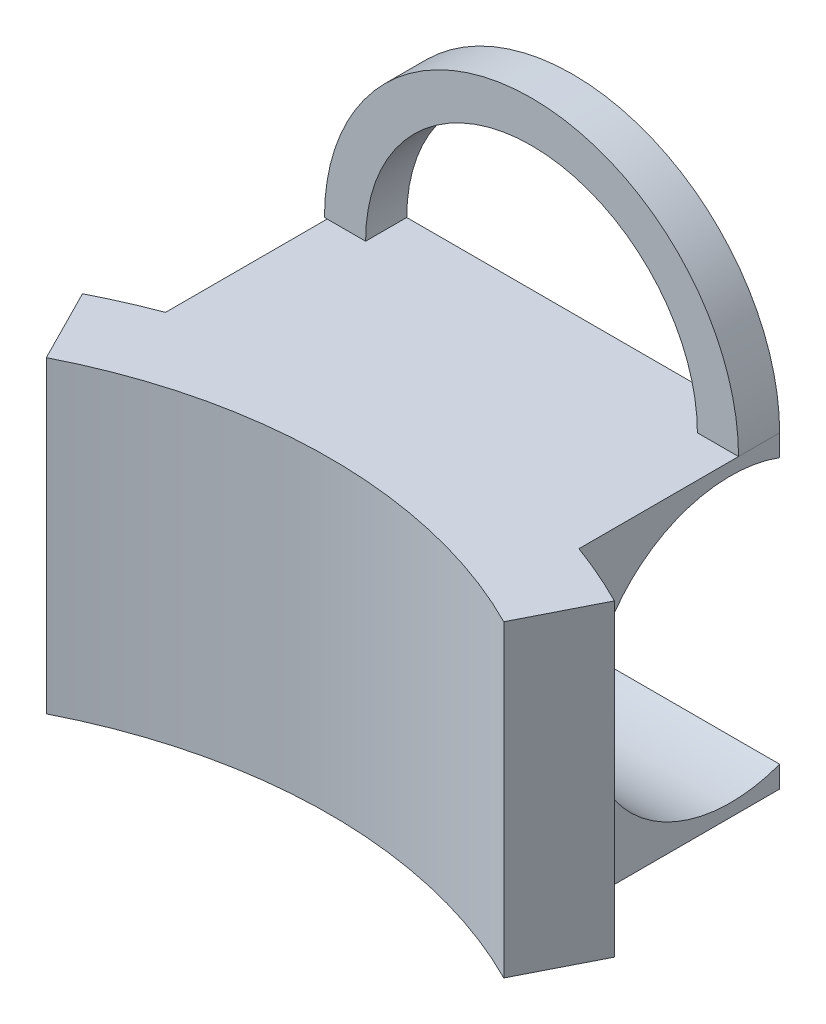
SolidWorks part; units mm, degrees
material "PVC 0.007 Plasticized"
ref_plane "Front Plane" through (0, 0, 0) normal (0, 0, 1) x (1, 0, 0)
ref_plane "Top Plane" through (0, 0, 0) normal (0, 1, 0) x (1, 0, 0)
ref_plane "Right Plane" through (0, 0, 0) normal (1, 0, 0) x (0, 0, -1)
ref_axis "X-Axis" through (-88.99, 0, 0) along (1, 0, 0)
ref_axis "Y-Axis" through (0, 55, 0) along (0, -1, 0)
ref_axis "Z-Axis" through (0, 0, 55) along (0, 0, -1)
sketch "Sketch2" plane through (0, 0, 0) normal (0, 1, 0) x (1, 0, 0)
  line L1 (-6.35, 0) -> (6.35, 0)
  line L2 (-6.35, 0) -> (-6.35, -6.35)
  line L3 (-6.35, -6.35) -> (6.35, -6.35)
  line L4 (6.35, 0) -> (6.35, -6.35)
  point P4 (0, -6.35)
  dimension "D1" = 6.35
  dimension "D2" = 12.7
extrude "Boss-Extrude1" add sketch "Sketch2" against normal blind 9.525
sketch "Sketch3" plane through (0, 0, 0) normal (0, 1, 0) x (1, 0, 0)
  arc A0 (-7.5546, -8.1773) -> (7.7179, -8.1773) centre (0.0817, -23.2191) cw
extrude "Extrude-Thin1" add sketch "Sketch3" against normal blind 9.525 thin thin type mid plane wall 2.54
sketch "Sketch4" plane through (0, 0, 0) normal (1, 0, 0) x (0, 0, -1)
  line L0 (0, -9.525) -> (0, 0) construction
  circle A0 centre (-1.517, -4.7625) radius 4.37
  point P4 (0, -4.7625)
extrude "Cut-Extrude1" cut sketch "Sketch4" against normal through all both and the other way through all contours A0
sketch "Sketch6" plane through (0, 0, 0) normal (0, 0, 1) x (1, 0, 0)
  line L0 (7.143, 0) -> (-6.9797, 0) construction
  arc A0 (-6.4331, 0) -> (6.35, 0) centre (-0.0415, 0) cw
extrude "Extrude-Thin3" add sketch "Sketch6" along normal blind 1.27 thin thin type one direction wall 1.27
